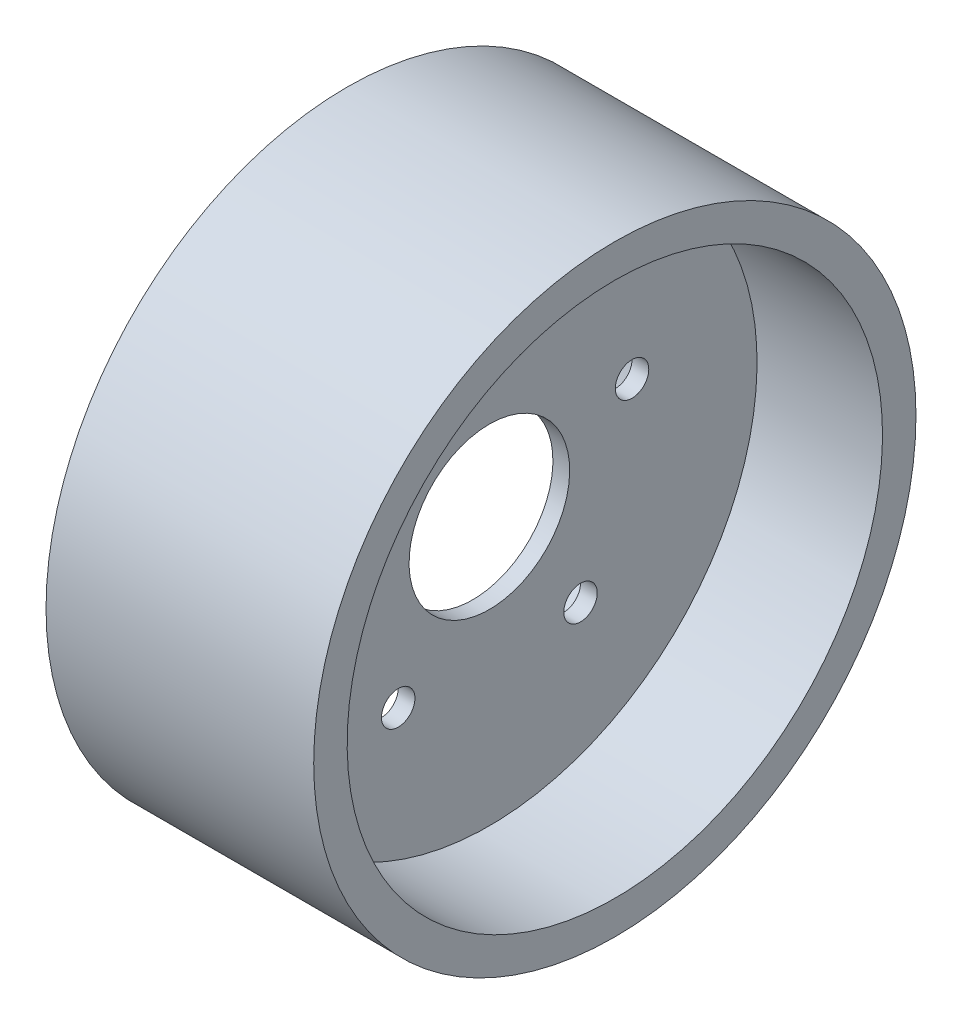
SolidWorks part; units mm, degrees
material "1060 Alloy"
ref_plane "Front Plane" through (0, 0, 0) normal (0, 0, 1) x (1, 0, 0)
ref_plane "Top Plane" through (0, 0, 0) normal (0, 1, 0) x (1, 0, 0)
ref_plane "Right Plane" through (0, 0, 0) normal (1, 0, 0) x (0, 0, -1)
sketch "Sketch1" plane through (0, 0, 0) normal (0, 0, 1) x (1, 0, 0)
  line L0 (0, 0) -> (0, 101.6)
  line L1 (0, 101.6) -> (6.35, 101.6)
  line L2 (6.35, 101.6) -> (6.35, 0)
  line L3 (6.35, 0) -> (0, 0)
  line L5 (-47.625, 114.3) -> (53.975, 114.3)
  line L6 (-47.625, 114.3) -> (-47.625, 101.6)
  line L7 (-47.625, 101.6) -> (53.975, 101.6)
  line L8 (53.975, 114.3) -> (53.975, 101.6)
  point P9 (3.175, 101.6)
  point P10 (3.175, 101.6)
  dimension "D1" = 101.6
  dimension "D2" = 6.35
  dimension "D3" = 101.6
  dimension ".5" = 12.7
revolve "Revolve1" add sketch "Sketch1" angle 360 about L3 region at (3.175, 50.8, 0) region at (3.175, 107.95, 0)
sketch "Sketch2" plane through (6.35, 0, 0) normal (1, 0, 0) x (0, 0, -1)
  line L0 (0, 57.15) -> (-54.1556, 18.2562) construction
  line L1 (-54.1556, 18.2562) -> (-34.5994, -45.4863) construction
  line L2 (54.1556, 18.2562) -> (34.5994, -45.4863) construction
  line L3 (34.5994, -45.4863) -> (-34.5994, -45.4863) construction
  line L4 (0, 57.15) -> (54.1556, 18.2562) construction
  circle A0 centre (0, 0) radius 57.15
  circle A1 centre (0, 0) radius 30.48
  point P3 (0, 57.15)
  point P4 (34.5994, -45.4863)
  point P5 (54.1556, 18.2562)
  point P6 (-34.5994, -45.4863)
  point P7 (-54.1556, 18.2562)
  dimension "D1" = 114.3
  dimension "D3" = 60.96
  dimension "D2" = 66.675
extrude "Cut-Extrude2" cut sketch "Sketch2" against normal through all contours A1
hole_wizard "1/2 (0.5) Diameter Hole2" positions "Sketch5" profile "Sketch6" hole size "1/2" standard "ANSI Inch" end condition through all
sketch "Sketch5" plane through (6.35, 0, 0) normal (1, 0, 0) x (0, 0, -1)
  point P0 (-54.1556, 18.2562)
  point P3 (0, 57.15)
  point P6 (54.1556, 18.2562)
  point P9 (34.5994, -45.4863)
  point P12 (-34.5994, -45.4863)
sketch "Sketch6" plane through (6.35, 18.2562, 54.1556) normal (0, 1, 0) x (0, 0, -1)
  line L0 (0, 0) -> (0, 53.975)
  line L1 (0, 53.975) -> (6.35, 53.975)
  line L2 (6.35, 53.975) -> (6.35, 0)
  line L5 (6.35, 0) -> (0, 0)
  line L11 (0, -6.35) -> (0, 107.95) construction
  dimension "Thru Hole Dia." = 12.7
  dimension "Thru Hole Depth" = 53.975
